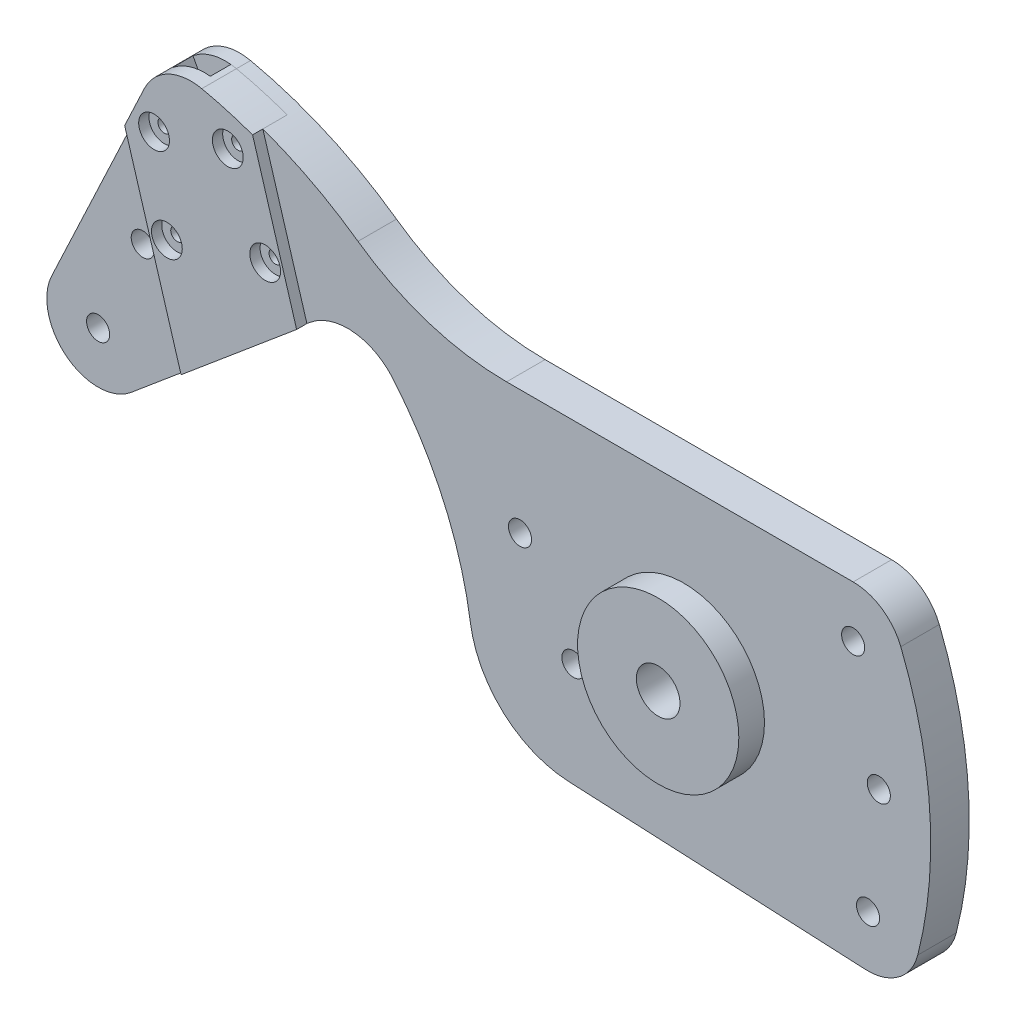
SolidWorks part; units mm, degrees
ref_plane "Front Plane" through (0, 0, 0) normal (0, 0, 1) x (1, 0, 0)
ref_plane "Top Plane" through (0, 0, 0) normal (0, 1, 0) x (1, 0, 0)
ref_plane "Right Plane" through (0, 0, 0) normal (1, 0, 0) x (0, 0, -1)
sketch "Sketch1" plane through (0, 0, 0) normal (0, 0, 1) x (1, 0, 0)
  line L1 (-4.25, -4.25) -> (4.25, -4.25) construction
  line L2 (-4.25, -4.25) -> (-4.25, 4.25) construction
  line L3 (-4.25, 4.25) -> (4.25, 4.25) construction
  line L4 (4.25, -4.25) -> (4.25, 4.25) construction
  line L5 (-4.25, -4.25) -> (4.25, 4.25) construction
  line L6 (-4.25, 4.25) -> (4.25, -4.25) construction
  line L7 (35.3984, -31.7883) -> (-22.5002, -28.984)
  line L9 (-114.4671, 24.4556) -> (-123.1671, 5.9556)
  line L10 (-107.6899, -5.9604) -> (-72.8648, 23.2613)
  line L11 (-114.4671, 24.4556) -> (-103.0859, 48.6569)
  line L16 (-65.4725, 14.4515) -> (-108.3178, -21.5) construction
  line L17 (50.9822, -33.5) -> (-177.2181, -33.5) construction
  line L20 (-34.5382, 32.4) -> (32.9822, 32.4)
  circle A0 centre (0, 0) radius 4.25
  circle A1 centre (-31.9178, 8.2) radius 2.25
  circle A2 centre (-21.5178, -8.7) radius 2.25
  circle A3 centre (32.9822, 22.4) radius 2.25
  circle A4 centre (37.9822, -0.1) radius 2.25
  circle A5 centre (35.8822, -21.8) radius 2.25
  circle A6 centre (35.8822, -21.8) radius 2.25 construction
  circle A7 centre (37.9822, -0.1) radius 2.25 construction
  circle A8 centre (32.9822, 22.4) radius 2.25 construction
  circle A9 centre (-31.9178, 8.2) radius 2.25 construction
  circle A10 centre (-21.5178, -8.7) radius 2.25 construction
  arc A12 (-41.6083, -11.6627) -> (-22.5002, -28.984) centre (-21.5178, -8.7) ccw
  arc A13 (32.5913, -31.6523) -> (28.0429, 32.4) centre (-33.3577, -4.1478) ccw construction
  arc A14 (45.5723, -24.2704) -> (42.2664, 26.1153) centre (-33.3577, -4.1478) ccw
  arc A15 (35.3984, -31.7883) -> (45.5723, -24.2704) centre (35.8822, -21.8) ccw
  arc A16 (42.2664, 26.1153) -> (32.9822, 32.4) centre (32.9822, 22.4) ccw
  circle A17 centre (-105.4178, 20.2) radius 2.25
  circle A18 centre (-33.3577, -4.1478) radius 81.4546 construction
  circle A19 centre (-114.1178, 1.7) radius 2.25
  circle A21 centre (-105.4178, 20.2) radius 2.25 construction
  circle A22 centre (-114.1178, 1.7) radius 2.25 construction
  circle A23 centre (-105.4178, 20.2) radius 10 construction
  arc A24 (-123.1671, 5.9556) -> (-107.6899, -5.9604) centre (-114.1178, 1.7) ccw
  arc A27 (-91.9187, 54.1744) -> (-103.0859, 48.6569) centre (-94.0366, 44.4013) ccw
  circle A31 centre (-33.3577, -4.1478) radius 71.4546 construction
  arc A32 (-41.6083, -11.6627) -> (-56.6627, 21.8438) centre (-108.3178, -21.5) ccw
  arc A33 (-31.0568, -26.628) -> (-91.9187, 54.1744) centre (-108.3178, -21.5) ccw
  arc A34 (-63.487, 41.6328) -> (-34.5382, 32.4) centre (-34.5382, 82.4) ccw
  arc A35 (-56.6627, 21.8438) -> (-72.8648, 23.2613) centre (-65.4725, 14.4515) ccw
  circle A36 centre (-65.4725, 14.4515) radius 10.5004 construction
  circle A37 centre (-108.3178, -21.5) radius 67.4309 construction
  circle A38 centre (-108.3178, -21.5) radius 77.4309 construction
  circle A39 centre (-108.3178, -21.5) radius 10.5004 construction
  circle A40 centre (-108.3178, -21.5) radius 11.5004 construction
  circle A41 centre (0, 0) radius 33 construction
  point P35 (50.3427, -4.5217)
  point P37 (37.1696, 16.7103)
  point P54 (-36.0565, -0.0269)
  point P75 (-40.8381, -1.4887)
  dimension "D1" = 8.5
  dimension "D3" = 10
  dimension "D5" = 50
  dimension "D7" = 40
  dimension "D4" = 10
  dimension "D2" = 10
  dimension "D8" = 1
extrude "Boss-Extrude1" add sketch "Sketch1" along normal mid plane 9.5 contours A0 L4 L3 | A0 L1 L4 | A0 L2 L1 | A0 L3 L2 | A35 A32 A12 A33 A27 L11 L9 A24 L10 A17 A19 region at (4.1562, 2.3635, 0) region at (-82.595, 21.4109, 0)
sketch "Sketch2" plane through (0, 0, 0) normal (0, 0, 1) x (1, 0, 0)
  line L0 (-94.0366, 44.4013) -> (-96.9145, 53.9782) construction
  line L1 (-78.2271, 18.7618) -> (-72.8648, 23.2613)
  line L2 (-94.0366, 44.4013) -> (-84.6999, 13.3304) construction
  line L3 (-92.0846, 44.9879) -> (-78.2271, 18.7618)
  line L4 (-95.0124, 54.3536) -> (-94.0366, 44.4013) construction
  line L5 (-94.0366, 44.4013) -> (-90.5122, 8.4534) construction
  line L6 (-98.7084, 53.2429) -> (-94.0366, 44.4013) construction
  line L7 (-94.0366, 44.4013) -> (-79.7943, 17.4467) construction
  line L8 (-100.3823, 52.1299) -> (-95.9887, 43.8147)
  line L9 (-93.0022, 54.3476) -> (-92.0846, 44.9879)
  line L12 (-92.369, 6.8953) -> (-78.2271, 18.7618)
  line L13 (-107.6899, -5.9604) -> (-72.8648, 23.2613) construction
  line L14 (-101.3327, 53.9285) -> (-91.0539, 34.4751) construction
  line L15 (-93.2007, 56.3721) -> (-91.0539, 34.4751) construction
  line L16 (-95.9887, 43.8147) -> (-92.369, 6.8953)
  line L18 (-97.0194, 54.3274) -> (-78.2271, 18.7618) construction
  line L19 (-97.0194, 54.3274) -> (-92.369, 6.8953) construction
  line L20 (-92.369, 6.8953) -> (-107.6899, -5.9604)
  line L22 (-94.0366, 44.4013) -> (-90.3786, 7.0905) construction
  line L23 (-94.0366, 44.4013) -> (-79.9955, 17.8274) construction
  arc A0 (-93.0022, 54.3476) -> (-100.3823, 52.1299) centre (-94.0366, 44.4013) ccw
  arc A1 (-95.0124, 54.3536) -> (-98.7084, 53.2429) centre (-94.0366, 44.4013) ccw construction
  arc A2 (-93.2007, 56.3721) -> (-101.3327, 53.9285) centre (-94.0366, 44.4013) ccw construction
  arc A3 (-91.9187, 54.1744) -> (-103.0859, 48.6569) centre (-94.0366, 44.4013) ccw construction
  point P33 (-96.9145, 53.9782)
  dimension "D3" = 7
  dimension "D4" = 20
  dimension "D1" = 2
  dimension "D2" = 2
extrude "Cut-Extrude1" cut sketch "Sketch2" against normal mid plane 4 contours A0 L8 L12 L9 region at (-89.8285, 28.8905, 0)
ref_plane "Plane1" through (-20.0256, 66.6414, 0) normal (-0.2878, 0.9577, 0) x (0.9577, 0.2878, 0)
sketch "Sketch4" plane through (0, 0, 4.75) normal (0, 0, 1) x (1, 0, 0)
  line L10 (-101.2193, 42.2429) -> (-86.8539, 46.5597) construction
  line L11 (-17.9186, 67.2745) -> (-22.1325, 66.0083) construction
  line L12 (-98.7212, 25.2426) -> (-79.5673, 30.9983) construction
  line L13 (-94.0366, 44.4013) -> (-89.1443, 28.1205) construction
  line L15 (-92.0846, 44.9879) -> (-93.0022, 54.3476)
  line L16 (-78.2271, 18.7618) -> (-92.0846, 44.9879)
  line L17 (-92.369, 6.8953) -> (-78.2271, 18.7618)
  line L18 (-95.9887, 43.8147) -> (-92.369, 6.8953)
  line L19 (-100.3823, 52.1299) -> (-95.9887, 43.8147)
  line L20 (-92.0846, 44.9879) -> (-93.0022, 54.3476) construction
  line L21 (-78.2271, 18.7618) -> (-92.0846, 44.9879) construction
  line L22 (-92.369, 6.8953) -> (-78.2271, 18.7618) construction
  line L23 (-95.9887, 43.8147) -> (-92.369, 6.8953) construction
  line L24 (-100.3823, 52.1299) -> (-95.9887, 43.8147) construction
  circle A0 centre (-98.7212, 25.2426) radius 1.25
  circle A1 centre (-101.2193, 42.2429) radius 1.25
  circle A2 centre (-86.8539, 46.5597) radius 1.25
  circle A3 centre (-79.5673, 30.9983) radius 1.25
  arc A7 (-93.0022, 54.3476) -> (-100.3823, 52.1299) centre (-94.0366, 44.4013) ccw
  arc A8 (-93.0022, 54.3476) -> (-100.3823, 52.1299) centre (-94.0366, 44.4013) ccw construction
  point P13 (-94.0366, 44.4013)
  dimension "D3" = 2.5
  dimension "D2" = 17
  dimension "D4" = 15
  dimension "D5" = 20
  dimension "D1" = 0
extrude "Cut-Extrude2" cut sketch "Sketch4" against normal through all
sketch "Sketch5" plane through (0, 0, 4.75) normal (0, 0, 1) x (1, 0, 0)
  circle A49 centre (-101.2193, 42.2429) radius 3
  circle A50 centre (-86.8539, 46.5597) radius 3
  circle A51 centre (-79.5673, 30.9983) radius 3
  circle A52 centre (-98.7212, 25.2426) radius 3
  dimension "D1" = 6
extrude "Cut-Extrude3" cut sketch "Sketch5" against normal blind 2
sketch "Sketch3" plane through (-20.0256, 66.6414, 0) normal (-0.2878, 0.9577, 0) x (0.9577, 0.2878, 0)
  line L0 (-90.7804, 2) -> (-63.7804, 2)
  line L1 (-63.7804, 2) -> (-63.7804, -4.75)
  line L2 (-72.4396, -4.75) -> (-48.8199, -4.75) construction
  line L3 (-90.7804, 2) -> (-90.7804, -4.75)
  line L4 (-116.2426, -4.75) -> (-84.7222, -4.75) construction
  line L11 (-79.3187, 2) -> (-75.2421, 2) construction
  point P3 (-77.2804, 2)
  point P11 (-77.2804, 2)
  dimension "D1" = 27
split "Split3" trim tools "Sketch3" bodies to split 111 resulting bodies 112 113
sketch "Sketch6" plane through (0, 0, 4.75) normal (0, 0, 1) x (1, 0, 0)
  line L6 (-95.9577, 3.8841) -> (-106.9455, 40.4497)
  line L7 (-106.9455, 40.4497) -> (-123.1671, 5.9556)
  line L8 (-107.6899, -5.9604) -> (-95.9577, 3.8841)
  line L9 (-95.9577, 3.8841) -> (-106.9455, 40.4497)
  line L10 (-106.9455, 40.4497) -> (-123.1671, 5.9556)
  line L11 (-107.6899, -5.9604) -> (-95.9577, 3.8841)
  line L17 (-82.0221, 51.3292) -> (-73.4422, 22.7768)
  line L18 (-73.4422, 22.7768) -> (-72.8648, 23.2613)
  line L19 (-22.5002, -28.984) -> (35.3984, -31.7883)
  line L20 (32.9822, 32.4) -> (-34.5382, 32.4)
  line L21 (-82.0221, 51.3292) -> (-73.4422, 22.7768)
  line L22 (-73.4422, 22.7768) -> (-72.8648, 23.2613)
  line L23 (-22.5002, -28.984) -> (35.3984, -31.7883)
  line L24 (32.9822, 32.4) -> (-34.5382, 32.4)
  circle A0 centre (0, 0) radius 15.71
  circle A1 centre (-21.5178, -8.7) radius 7.5 construction
  arc A2 (-123.1671, 5.9556) -> (-107.6899, -5.9604) centre (-114.1178, 1.7) ccw
  arc A3 (-123.1671, 5.9556) -> (-107.6899, -5.9604) centre (-114.1178, 1.7) ccw
  arc A19 (-56.6627, 21.8438) -> (-72.8648, 23.2613) centre (-65.4725, 14.4515) ccw
  arc A20 (-41.6083, -11.6627) -> (-56.6627, 21.8438) centre (-108.3178, -21.5) ccw
  arc A21 (-41.6083, -11.6627) -> (-22.5002, -28.984) centre (-21.5178, -8.7) ccw
  arc A22 (35.3984, -31.7883) -> (45.5723, -24.2704) centre (35.8822, -21.8) ccw
  arc A23 (45.5723, -24.2704) -> (42.2664, 26.1153) centre (-33.3577, -4.1478) ccw
  arc A24 (42.2664, 26.1153) -> (32.9822, 32.4) centre (32.9822, 22.4) ccw
  arc A25 (-63.487, 41.6328) -> (-34.5382, 32.4) centre (-34.5382, 82.4) ccw
  arc A26 (-63.487, 41.6328) -> (-82.0221, 51.3292) centre (-108.3178, -21.5) ccw
  arc A27 (-56.6627, 21.8438) -> (-72.8648, 23.2613) centre (-65.4725, 14.4515) ccw
  arc A28 (-41.6083, -11.6627) -> (-56.6627, 21.8438) centre (-108.3178, -21.5) ccw
  arc A29 (-41.6083, -11.6627) -> (-22.5002, -28.984) centre (-21.5178, -8.7) ccw
  arc A30 (35.3984, -31.7883) -> (45.5723, -24.2704) centre (35.8822, -21.8) ccw
  arc A31 (45.5723, -24.2704) -> (42.2664, 26.1153) centre (-33.3577, -4.1478) ccw
  arc A32 (42.2664, 26.1153) -> (32.9822, 32.4) centre (32.9822, 22.4) ccw
  arc A33 (-63.487, 41.6328) -> (-34.5382, 32.4) centre (-34.5382, 82.4) ccw
  arc A34 (-63.487, 41.6328) -> (-82.0221, 51.3292) centre (-108.3178, -21.5) ccw
  dimension "D3" = 15
  dimension "D1" = 0
  dimension "D2" = 0
extrude "Cut-Extrude4" cut sketch "Sketch6" against normal blind 2
sketch "Sketch7" plane through (0, 0, 4.75) normal (0, 0, 1) x (1, 0, 0)
  circle A2 centre (0, 0) radius 15.71
  circle A3 centre (0, 0) radius 15.71
  circle A5 centre (0, 0) radius 4.25
  circle A6 centre (0, 0) radius 4.25
  dimension "D1" = 0
  dimension "D2" = 0
extrude "Boss-Extrude2" add sketch "Sketch7" along normal blind 3
